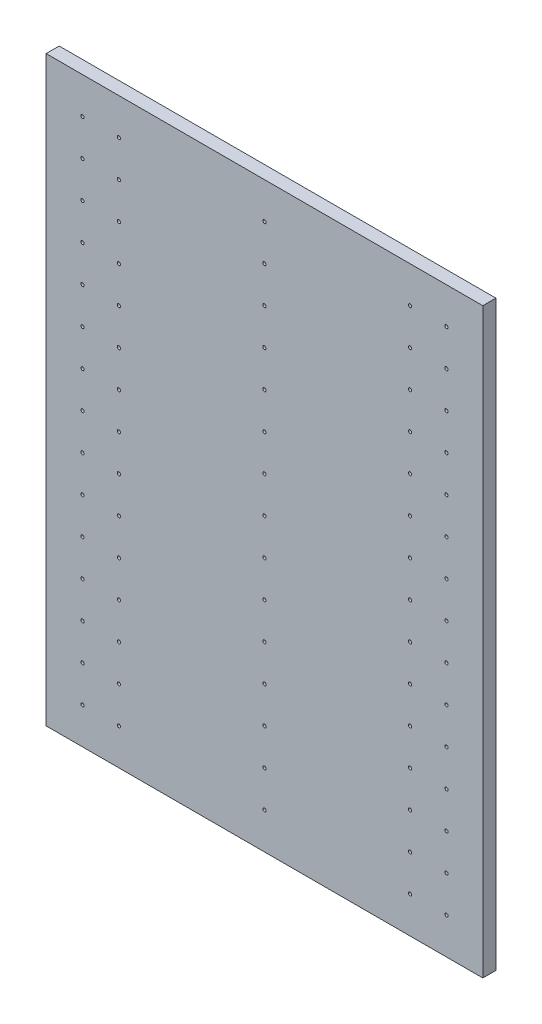
SolidWorks part; units mm, degrees
ref_plane "Спереди" through (0, 0, 0) normal (0, 0, 1) x (1, 0, 0)
ref_plane "Сверху" through (0, 0, 0) normal (0, 1, 0) x (1, 0, 0)
ref_plane "Справа" through (0, 0, 0) normal (1, 0, 0) x (0, 0, -1)
sketch "Эскиз1" plane through (0, 0, 0) normal (0, 0, 1) x (1, 0, 0)
  line L1 (0, 0) -> (600, 0)
  line L2 (0, 0) -> (0, 800)
  line L3 (0, 800) -> (600, 800)
  line L4 (600, 0) -> (600, 800)
extrude "Бобышка-Вытянуть1" add sketch "Эскиз1" along normal blind 18
sketch "Эскиз2" plane through (0, 0, 18) normal (0, 0, 1) x (1, 0, 0)
  circle A0 centre (550, 50) radius 2.25
  circle A1 centre (300, 50) radius 2.25
  circle A2 centre (500, 50) radius 2.25
  circle A3 centre (100, 50) radius 2.25
  circle A4 centre (50, 50) radius 2.25
  circle A60 centre (550, 100) radius 2.25
  circle A61 centre (300, 100) radius 2.25
  circle A62 centre (500, 100) radius 2.25
  circle A63 centre (100, 100) radius 2.25
  circle A64 centre (50, 100) radius 2.25
  circle A65 centre (550, 150) radius 2.25
  circle A66 centre (300, 150) radius 2.25
  circle A67 centre (500, 150) radius 2.25
  circle A68 centre (100, 150) radius 2.25
  circle A69 centre (50, 150) radius 2.25
  circle A70 centre (550, 200) radius 2.25
  circle A71 centre (300, 200) radius 2.25
  circle A72 centre (500, 200) radius 2.25
  circle A73 centre (100, 200) radius 2.25
  circle A74 centre (50, 200) radius 2.25
  circle A75 centre (550, 250) radius 2.25
  circle A76 centre (300, 250) radius 2.25
  circle A77 centre (500, 250) radius 2.25
  circle A78 centre (100, 250) radius 2.25
  circle A79 centre (50, 250) radius 2.25
  circle A80 centre (550, 300) radius 2.25
  circle A81 centre (300, 300) radius 2.25
  circle A82 centre (500, 300) radius 2.25
  circle A83 centre (100, 300) radius 2.25
  circle A84 centre (50, 300) radius 2.25
  circle A85 centre (550, 350) radius 2.25
  circle A86 centre (300, 350) radius 2.25
  circle A87 centre (500, 350) radius 2.25
  circle A88 centre (100, 350) radius 2.25
  circle A89 centre (50, 350) radius 2.25
  circle A90 centre (550, 400) radius 2.25
  circle A91 centre (300, 400) radius 2.25
  circle A92 centre (500, 400) radius 2.25
  circle A93 centre (100, 400) radius 2.25
  circle A94 centre (50, 400) radius 2.25
  circle A95 centre (550, 450) radius 2.25
  circle A96 centre (300, 450) radius 2.25
  circle A97 centre (500, 450) radius 2.25
  circle A98 centre (100, 450) radius 2.25
  circle A99 centre (50, 450) radius 2.25
  circle A100 centre (550, 500) radius 2.25
  circle A101 centre (300, 500) radius 2.25
  circle A102 centre (500, 500) radius 2.25
  circle A103 centre (100, 500) radius 2.25
  circle A104 centre (50, 500) radius 2.25
  circle A105 centre (550, 550) radius 2.25
  circle A106 centre (300, 550) radius 2.25
  circle A107 centre (500, 550) radius 2.25
  circle A108 centre (100, 550) radius 2.25
  circle A109 centre (50, 550) radius 2.25
  circle A110 centre (550, 600) radius 2.25
  circle A111 centre (300, 600) radius 2.25
  circle A112 centre (500, 600) radius 2.25
  circle A113 centre (100, 600) radius 2.25
  circle A114 centre (50, 600) radius 2.25
  circle A115 centre (550, 650) radius 2.25
  circle A116 centre (300, 650) radius 2.25
  circle A117 centre (500, 650) radius 2.25
  circle A118 centre (100, 650) radius 2.25
  circle A119 centre (50, 650) radius 2.25
  circle A120 centre (550, 700) radius 2.25
  circle A121 centre (300, 700) radius 2.25
  circle A122 centre (500, 700) radius 2.25
  circle A123 centre (100, 700) radius 2.25
  circle A124 centre (50, 700) radius 2.25
  circle A125 centre (550, 750) radius 2.25
  circle A126 centre (300, 750) radius 2.25
  circle A127 centre (500, 750) radius 2.25
  circle A128 centre (100, 750) radius 2.25
  circle A129 centre (50, 750) radius 2.25
  point P3 (0, 0)
  dimension "D1" = 15
extrude "Вырез-Вытянуть1" cut sketch "Эскиз2" against normal blind 9
